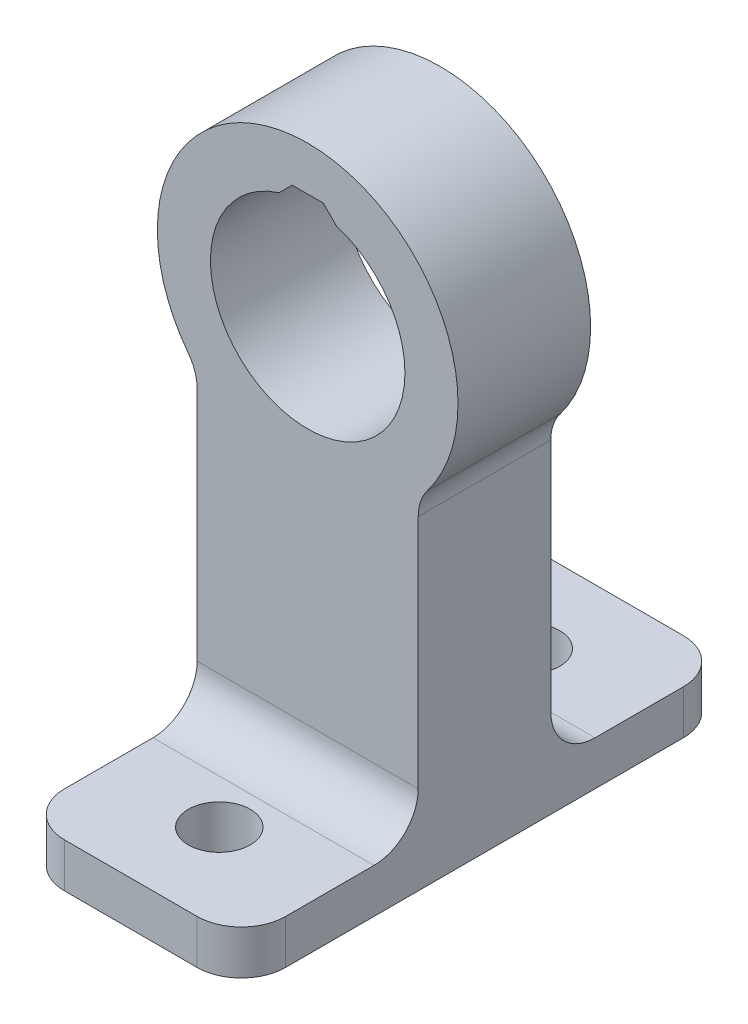
SolidWorks part; units mm, degrees
ref_plane "Front Plane" through (0, 0, 0) normal (0, 0, 1) x (1, 0, 0)
ref_plane "Top Plane" through (0, 0, 0) normal (0, 1, 0) x (1, 0, 0)
ref_plane "Right Plane" through (0, 0, 0) normal (1, 0, 0) x (0, 0, -1)
sketch "Sketch1" plane through (0, 0, 0) normal (0, 0, 1) x (1, 0, 0)
  line L0 (-12.5, -11.5217) -> (-12.5, -50)
  line L1 (12.5, -11.5217) -> (12.5, -50)
  line L7 (-12.5, -50) -> (12.5, -50)
  line L8 (-3.25, 10.5089) -> (-1.7589, 12)
  line L9 (-1.7589, 12) -> (1.7589, 12)
  line L10 (1.7589, 12) -> (3.25, 10.5089)
  arc A0 (-3.25, 10.5089) -> (3.25, 10.5089) centre (0, 0) ccw
  arc A1 (12.5, -11.5217) -> (-12.5, -11.5217) centre (0, 0) ccw
  point P9 (0, 12)
  point P12 (0, 0)
  point P13 (3.2218, 10.5176)
  dimension "D1" = 22
  dimension "D2" = 6
  dimension "D5" = 12
  dimension "D3" = 50
  dimension "D4" = 25
  dimension "D6" = 45
  dimension "D7" = 6.5
extrude "Boss-Extrude1" add sketch "Sketch1" along normal blind 15
sketch "Sketch6" plane through (0, -50, 0) normal (0, -1, 0) x (1, 0, 0)
  line L0 (12.5, 15) -> (12.5, 0) construction
  line L1 (-12.5, 15) -> (12.5, 15)
  line L2 (-12.5, 15) -> (-12.5, 35)
  line L3 (-12.5, 35) -> (12.5, 35)
  line L4 (12.5, 15) -> (12.5, 35)
  line L5 (-12.5, 0) -> (12.5, 0)
  line L6 (-12.5, 0) -> (-12.5, -20)
  line L7 (-12.5, -20) -> (12.5, -20)
  line L8 (12.5, 0) -> (12.5, -20)
  circle A0 centre (0, 25) radius 3.5
  circle A1 centre (0, -10) radius 3.5
  point P16 (0, 0)
  dimension "D4" = 7
  dimension "D1" = 20
  dimension "D2" = 10
  dimension "D3" = 10
extrude "Boss-Extrude4" add sketch "Sketch6" against normal blind 5
fillet "Fillet4" radius 5 8 edges at (-12.5, -47.5, -20) (12.5, -47.5, -20) (-12.5, -47.5, 35) (12.5, -47.5, 35) (0, -45, 15) (0, -45, 0) (12.5, -11.5217, 7.5) (-12.5, -11.5217, 7.5)
